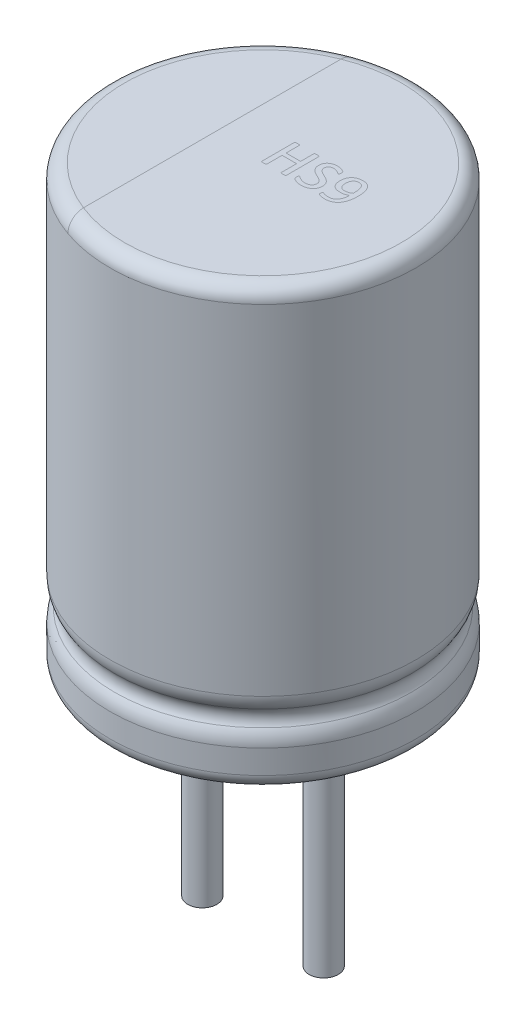
SolidWorks part; units mm, degrees
ref_plane "Спереди" through (0, 0, 0) normal (0, 0, 1) x (1, 0, 0)
ref_plane "Сверху" through (0, 0, 0) normal (0, 1, 0) x (1, 0, 0)
ref_plane "Справа" through (0, 0, 0) normal (1, 0, 0) x (0, 0, -1)
sketch "Эскиз1" plane through (0, 0, 0) normal (1, 0, 0) x (0, 0, -1)
  line L0 (-8.5209, 0) -> (7.83, 0) construction
  line L1 (0, 14.2398) -> (0, -3.7231) construction
  line L2 (0, 0) -> (-2.85, 0)
  line L3 (-3.15, 0.3) -> (-3.15, 1)
  line L4 (-2.85, 9) -> (0, 9)
  line L5 (0, 9) -> (0, 0)
  line L6 (-3.15, 1.5) -> (-3.15, 8.7)
  arc A0 (-3.15, 1) -> (-3.15, 1.5) centre (-3.283, 1.25) ccw
  arc A1 (-2.85, 0) -> (-3.15, 0.3) centre (-2.85, 0.3) cw
  arc A2 (-3.15, 8.7) -> (-2.85, 9) centre (-2.85, 8.7) cw
  point P7 (-3.15, 1)
  point P10 (-3.15, 1.5)
  point P14 (-2.9998, 1.25)
  point P17 (-3.15, 0)
  dimension "D6" = 0.3
  dimension "D1" = 3.15
  dimension "D2" = 9
  dimension "D3" = 1
  dimension "D4" = 0.5
  dimension "D5" = 2.9998
revolve "Повернуть1" add sketch "Эскиз1" angle 360 about L1
fillet "Скругление1" radius 0.5 2 edges at (0, 1.5, 3.15) (0, 1, 3.15)
sketch "Эскиз2" plane through (0, 0, 0) normal (0, -1, 0) x (1, 0, 0)
  circle A0 centre (0, 0) radius 2.15
  dimension "D1" = 4.3
extrude "Вырез-Вытянуть1" cut sketch "Эскиз2" against normal blind 0.3
fillet "Скругление2" radius 0.3 1 edges at (0, 0, -2.15)
sketch "Эскиз3" plane through (0, 0.3, 0) normal (0, -1, 0) x (1, 0, 0)
  line L0 (-1.941, 0) -> (2.0247, 0) construction
  line L1 (0, 1.4014) -> (0, -0.8827) construction
  circle A1 centre (-1.25, 0) radius 0.3
  circle A2 centre (1.25, 0) radius 0.3
  dimension "D1" = 0.6
  dimension "D2" = 1.25
extrude "Бобышка-Вытянуть1" add sketch "Эскиз3" along normal blind 5 separate body
ref_plane "Плоскость1" through (0, 9.3, 0) normal (0, 1, 0) x (1, 0, 0)
sketch "Эскиз4" plane through (0, 9, 0) normal (0, 1, 0) x (1, 0, 0)
  line L0 (-1.0458, 2.9713) -> (-1.0458, -2.9713)
  circle A0 centre (0, 0) radius 3.15 construction
  arc A1 (-1.0458, 2.9713) -> (-1.0458, -2.9713) centre (0, 0) ccw
split line "Разделяющая линия1"
ref_plane "Плоскость2" through (0, 18.6, 0) normal (0, 1, 0) x (1, 0, 0)
sketch "Эскиз6" plane through (0, 18.6, 0) normal (0, 1, 0) x (1, 0, 0)
  line L0 (-2.85, 0) -> (2.85, 0) construction
  arc A0 (-1.0458, 2.6512) -> (-1.0458, -2.6512) centre (0, 0) ccw construction
  arc A1 (-1.0458, -2.6512) -> (-1.0458, 2.6512) centre (0, 0) ccw construction
  text T0 "           HS9" font "Calibri" height 0.7
split line "Разделяющая линия2"
